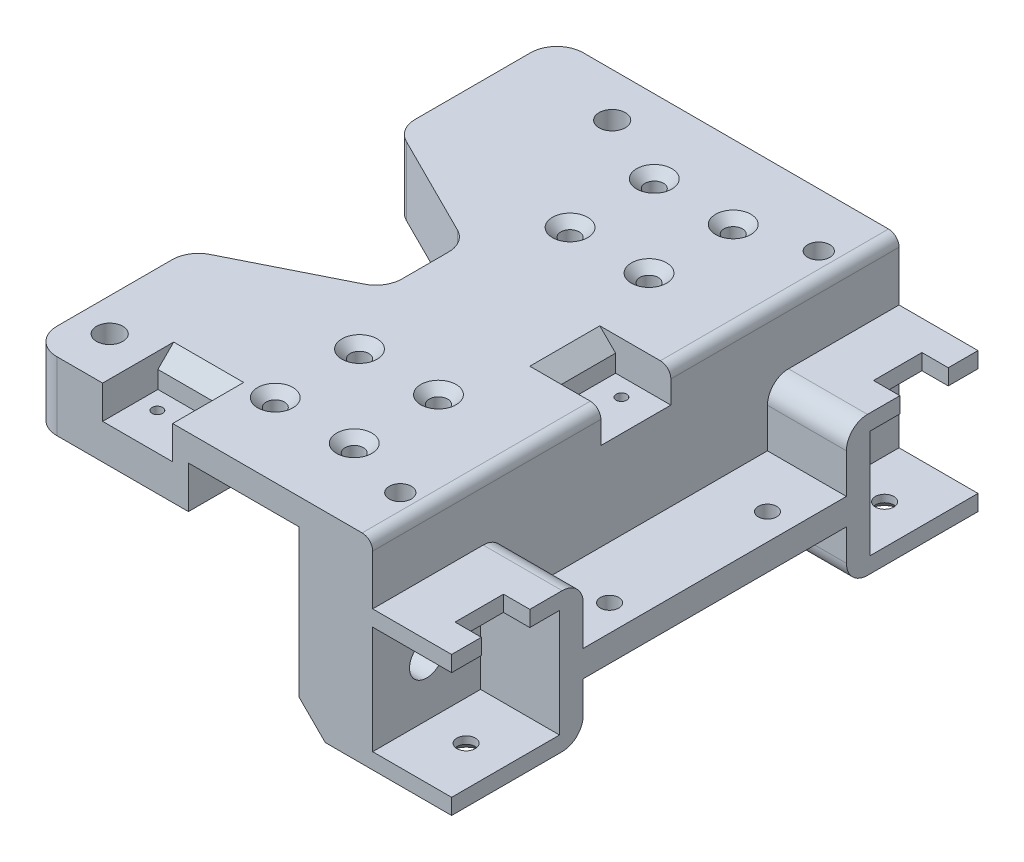
SolidWorks part; units mm, degrees
ref_plane "Front Plane" through (0, 0, 0) normal (0, 0, 1) x (1, 0, 0)
ref_plane "Top Plane" through (0, 0, 0) normal (0, 1, 0) x (1, 0, 0)
ref_plane "Right Plane" through (0, 0, 0) normal (1, 0, 0) x (0, 0, -1)
sketch "Sketch1" plane through (0, 0, 0) normal (0, 1, 0) x (1, 0, 0)
  line L0 (0, 50) -> (0, -50) construction
  line L1 (-10, 50) -> (10, 50)
  line L2 (-10, 50) -> (-10, -50)
  line L3 (-10, -50) -> (10, -50)
  line L4 (10, 50) -> (10, -50) construction
  line L5 (-10, 50) -> (10, -50) construction
  line L6 (-10, -50) -> (10, 50) construction
  line L7 (-7.5, 36) -> (7.5, 36) construction
  line L8 (-7.5, 36) -> (7.5, 20) construction
  line L9 (-10, 0) -> (10, 0) construction
  line L10 (-7.5, -36) -> (7.5, -20) construction
  line L11 (-7.5, -36) -> (7.5, -36) construction
  line L12 (-7.5, 20) -> (7.5, 20) construction
  line L13 (10, 50) -> (11, 50)
  line L14 (11, 50) -> (11, -50)
  line L15 (11, -50) -> (10, -50)
  circle A0 centre (-7.5, 36) radius 1.75
  circle A1 centre (7.5, 36) radius 1.75
  circle A2 centre (-7.5, 20) radius 1.75
  circle A3 centre (7.5, 20) radius 1.75
  circle A4 centre (7.5, -20) radius 1.75
  circle A5 centre (-7.5, -20) radius 1.75
  circle A6 centre (7.5, -36) radius 1.75
  circle A7 centre (-7.5, -36) radius 1.75
  point P0 (0, 0)
  point P16 (0, 36)
  dimension "D2" = 3.5
  dimension "D1" = 20
  dimension "D3" = 15
  dimension "D4" = 16
  dimension "D5" = 100
  dimension "D6" = 20
  dimension "D7" = 1
extrude "Boss-Extrude1" add sketch "Sketch1" along normal blind 5
sketch "Sketch2" plane through (11, 0, 0) normal (1, 0, 0) x (0, 0, -1)
  line L1 (-50, 5) -> (50, 5)
  line L2 (-50, 5) -> (-50, -33)
  line L3 (-50, -33) -> (50, -33)
  line L5 (50, 5) -> (50, -33)
  line L6 (50, 5) -> (50, 0) construction
  line L7 (-50, 5) -> (-50, 0) construction
  line L8 (-50, 5) -> (50, 5) construction
  dimension "D1" = 38
extrude "Boss-Extrude2" add sketch "Sketch2" along normal blind 14
sketch "Sketch3" plane through (25, 0, 0) normal (1, 0, 0) x (0, 0, -1)
  line L0 (0, 5) -> (0, -33) construction
  line L1 (-25, -18) -> (25, -18)
  line L2 (-25, -18) -> (-25, -23)
  line L3 (-25, -23) -> (25, -23)
  line L4 (25, -18) -> (25, -23)
  line L5 (50, 5) -> (-50, 5) construction
  line L6 (-50, -33) -> (50, -33) construction
  point P10 (0, -18)
  dimension "D1" = 5
  dimension "D2" = 50
  dimension "D3" = 10
extrude "Boss-Extrude3" add sketch "Sketch3" along normal blind 15
sketch "Sketch4" plane through (0, -18, 0) normal (0, 1, 0) x (1, 0, 0)
  line L0 (30, 0) -> (40, 0) construction
  line L2 (40, 25) -> (40, -25) construction
  line L3 (35, -15) -> (35, 15) construction
  circle A0 centre (35, 15) radius 1.75
  circle A1 centre (35, -15) radius 1.75
  point P8 (35, 0)
  dimension "D1" = 30
  dimension "D2" = 3.5
  dimension "D3" = 10
extrude "Cut-Extrude1" cut sketch "Sketch4" against normal through all
sketch "Sketch8" plane through (25, 0, 0) normal (1, 0, 0) x (0, 0, -1)
  line L0 (-50, 5) -> (-50, -33) construction
  line L1 (-50, -6.5) -> (-25, -6.5)
  line L2 (-50, -6.5) -> (-50, -9.5)
  line L3 (-50, -33) -> (-25, -33)
  line L4 (-25, -6.5) -> (-25, -33)
  line L5 (-50, -30) -> (-50, -33)
  line L6 (-50, -30) -> (-29.5, -30)
  line L8 (-50, -9.5) -> (-29.5, -9.5)
  line L9 (-29.5, -30) -> (-29.5, -9.5)
  line L10 (0, 20.9) -> (0, -20.9) construction
  line L11 (29.5, -30) -> (29.5, -9.5)
  line L12 (50, -9.5) -> (29.5, -9.5)
  line L13 (50, -30) -> (29.5, -30)
  line L14 (50, -30) -> (50, -33)
  line L15 (25, -6.5) -> (25, -33)
  line L16 (50, -33) -> (25, -33)
  line L17 (50, -6.5) -> (50, -9.5)
  line L18 (50, -6.5) -> (25, -6.5)
  line L19 (-50, -33) -> (50, -33) construction
  line L20 (-25, -18) -> (-25, -23) construction
  dimension "D1" = 3
  dimension "D3" = 3
  dimension "D4" = 20.5
  dimension "D5" = 20.5
extrude "Boss-Extrude6" add sketch "Sketch8" along normal blind 15
sketch "Sketch9" plane through (25, 0, 0) normal (1, 0, 0) x (0, 0, -1)
  line L0 (-50, -9.5) -> (-29.5, -30) construction
  line L1 (50, -9.5) -> (29.5, -30) construction
  circle A0 centre (-39.75, -19.75) radius 3.25
  circle A1 centre (39.75, -19.75) radius 3.25
  dimension "D1" = 6.5
extrude "Cut-Extrude3" cut sketch "Sketch9" against normal through all
sketch "Sketch10" plane through (11, 0, 0) normal (-1, 0, 0) x (0, 0, 1)
  circle A0 centre (-39.75, -19.75) radius 5.25
  circle A1 centre (39.75, -19.75) radius 5.25
  dimension "D1" = 10.5
extrude "Cut-Extrude4" cut sketch "Sketch10" against normal offset from surface (9 mm away) 5 up to face at (25, -19.75, 36.5)
sketch "Sketch11" plane through (0, -6.5, 0) normal (0, 1, 0) x (1, 0, 0)
  line L0 (40, -25) -> (40, -50) construction
  line L1 (40, -35.15) -> (35, -35.15)
  line L2 (40, -35.15) -> (40, -44.35)
  line L3 (40, -44.35) -> (35, -44.35)
  line L4 (35, -35.15) -> (35, -44.35)
  line L5 (35, -39.75) -> (40, -39.75) construction
  line L7 (-10, 0) -> (40, 0) construction
  line L8 (-10, 50) -> (-10, -50) construction
  line L9 (40, 25) -> (40, -25) construction
  line L10 (40, -35.15) -> (35, -35.15)
  line L11 (40, -44.35) -> (35, -44.35)
  line L12 (35, 39.75) -> (40, 39.75) construction
  line L13 (40, 44.35) -> (35, 44.35)
  line L14 (40, 35.15) -> (35, 35.15)
  line L15 (35, 35.15) -> (35, 44.35)
  line L16 (40, 44.35) -> (35, 44.35)
  line L17 (40, 35.15) -> (40, 44.35)
  line L18 (40, 35.15) -> (35, 35.15)
  line L19 (40, -50) -> (40, -29.5) construction
  point P22 (40, -39.75)
  line M7 (40, -50) -> (40, -25)
  dimension "D1" = 9.2
  dimension "D3" = 5
extrude "Cut-Extrude5" cut sketch "Sketch11" against normal up to next contours L1 L4 L3 M7 | L14 L17 L13 L15 region at (37.5, -6.5, 39.75) region at (37.5, -6.5, -39.75)
sketch "Sketch12" plane through (0, -30, 0) normal (0, 1, 0) x (1, 0, 0)
  line L0 (40, -39.75) -> (25, -39.75) construction
  line L1 (40, -29.5) -> (40, -50) construction
  line L2 (25, -25) -> (25, -50) construction
  line L3 (-20.9, 0) -> (20.9, 0) construction
  circle A0 centre (32.5, -39.75) radius 1.75
  circle A2 centre (32.5, 39.75) radius 1.75
  dimension "D1" = 3.5
extrude "Cut-Extrude6" cut sketch "Sketch12" against normal through all
sketch "Sketch13" plane through (-10, 0, 0) normal (-1, 0, 0) x (0, 0, 1)
  line L1 (-50, 5) -> (50, 5)
  line L2 (-50, 5) -> (-50, -8)
  line L3 (-50, -8) -> (50, -8)
  line L4 (50, 5) -> (50, -8)
  dimension "D1" = 13
extrude "Boss-Extrude7" add sketch "Sketch13" along normal blind 30
sketch "Sketch14" plane through (0, 5, 0) normal (0, 1, 0) x (1, 0, 0)
  line L6 (-27.65, 41.65) -> (-27.65, -41.23) construction
  line L12 (-21.15, 35.15) -> (40, 35.15) construction
  line L18 (-33.73, -35.15) -> (40, -35.15) construction
  circle A0 centre (-21.15, 41.65) radius 2.5
  circle A1 centre (-33.73, -41.23) radius 2.5
  circle A2 centre (-33.73, -41.23) radius 6.08 construction
  circle A3 centre (-21.15, 41.65) radius 6.5 construction
  dimension "D1" = 5
  dimension "D2" = 5
  dimension "D4" = 12.16
  dimension "D5" = 13
  dimension "D3" = 21.15
extrude "Cut-Extrude7" cut sketch "Sketch14" against normal through all
sketch "Sketch15" plane through (0, -8, 0) normal (0, -1, 0) x (1, 0, 0)
  line L0 (-40, -50) -> (-40, 50) construction
  line L1 (-29.63, 43.5971) -> (-33.73, 45.9643)
  line L2 (-33.73, 45.9643) -> (-37.83, 43.5971)
  line L3 (-37.83, 43.5971) -> (-37.83, 38.8629)
  line L4 (-37.83, 38.8629) -> (-33.73, 36.4957)
  line L5 (-33.73, 36.4957) -> (-29.63, 38.8629)
  line L6 (-29.63, 38.8629) -> (-29.63, 43.5971)
  line L7 (-17.05, -44.0171) -> (-17.05, -39.2829)
  line L8 (-17.05, -39.2829) -> (-21.15, -36.9157)
  line L9 (-21.15, -36.9157) -> (-25.25, -39.2829)
  line L10 (-25.25, -39.2829) -> (-25.25, -44.0171)
  line L11 (-25.25, -44.0171) -> (-21.15, -46.3843)
  line L12 (-21.15, -46.3843) -> (-17.05, -44.0171)
  circle A0 centre (-33.73, 41.23) radius 4.1 construction
  circle A1 centre (-21.15, -41.65) radius 4.1 construction
  dimension "D1" = 8.2
extrude "Cut-Extrude8" cut sketch "Sketch15" against normal blind 5
sketch "Sketch16" plane through (0, 5, 0) normal (0, 1, 0) x (1, 0, 0)
  line L0 (20, 39.75) -> (40, 39.75) construction
  line L1 (40, 39.75) -> (40, -39.75) construction
  line L2 (40, -39.75) -> (20, -39.75) construction
  line L3 (20, -39.75) -> (20, 39.75) construction
  line L4 (40, 50) -> (40, 29.5) construction
  line L5 (40, -29.5) -> (40, -50) construction
  circle A0 centre (20, 39.75) radius 2.1
  circle A1 centre (20, -39.75) radius 2.1
  dimension "D1" = 4.2
  dimension "D2" = 4.2
  dimension "D3" = 20
extrude "Cut-Extrude9" cut sketch "Sketch16" against normal blind 4
chamfer "Chamfer1" distance 1.6 angle 45 8 edges at (7.5, 5, 34.25) (-7.5, 5, 34.25) (7.5, 5, 18.25) (-7.5, 5, 18.25) (7.5, 5, -18.25) (-7.5, 5, -18.25) (7.5, 5, -34.25) (-7.5, 5, -34.25)
sketch "Sketch17" plane through (0, 5, 0) normal (0, 1, 0) x (1, 0, 0)
  line L0 (-40, 20) -> (-15, 7.5)
  line L1 (-40, -50) -> (-40, 50) construction
  line L2 (-15, 7.5) -> (-15, -7.5)
  line L3 (-15, -7.5) -> (-40, -20)
  line L4 (-40, -20) -> (-40, 20)
  point P5 (-15, 0)
  dimension "D1" = 15
  dimension "D2" = 25
  dimension "D3" = 40
extrude "Cut-Extrude10" cut sketch "Sketch17" against normal through all
chamfer "Chamfer2" distance 1.6 angle 45 2 edges at (32.5, -33, -41.5) (32.5, -33, 41.5)
chamfer "Chamfer3" distance 5 angle 45 1 edges at (11, -33, 0)
sketch "Sketch18" plane through (0, 1, 0) normal (0, 1, 0) x (1, 0, 0)
  circle A0 centre (20, 39.75) radius 1.75
  circle A1 centre (20, -39.75) radius 1.75
  dimension "D1" = 3.5
  dimension "D2" = 3.5
extrude "Cut-Extrude11" cut sketch "Sketch18" against normal blind 4
fillet "Fillet1" radius 5 6 edges at (-40, -1.5, 50) (-40, -1.5, 20) (-15, -1.5, 7.5) (-15, -1.5, -7.5) (-40, -1.5, -20) (-40, -1.5, -50)
fillet "Fillet2" radius 4 4 edges at (32.5, -33, -25) (32.5, -6.5, -25) (32.5, -33, 25) (32.5, -6.5, 25)
sketch "Sketch19" plane through (25, 0, 0) normal (1, 0, 0) x (0, 0, -1)
  line L0 (50, 5) -> (-50, 5) construction
  line L1 (-6.65, 5) -> (6.65, 5)
  line L2 (-6.65, 5) -> (-6.65, -1.3)
  line L3 (-6.65, -1.3) -> (6.65, -1.3)
  line L4 (6.65, 5) -> (6.65, -1.3)
  point P7 (0, 5)
  dimension "D1" = 13.3
  dimension "D2" = 6.3
extrude "Cut-Extrude12" cut sketch "Sketch19" against normal blind 10.5
sketch "Sketch20" plane through (0, -1.3, 0) normal (0, 1, 0) x (1, 0, 0)
  line L0 (19, 3.25) -> (19, -3.25) construction
  line L3 (14.5, 6.65) -> (14.5, -6.65) construction
  line L4 (18, 3.25) -> (18, -3.25) construction
  circle A0 centre (19, 3.25) radius 1
  circle A1 centre (19, -3.25) radius 1
  point P2 (14.5, 0)
  point P3 (19, 0)
  dimension "D1" = 2
  dimension "D2" = 6.5
  dimension "D3" = 3.5
extrude "Cut-Extrude13" cut sketch "Sketch20" against normal blind 3
chamfer "Chamfer4" distance 3 angle 45 1 edges at (14.5, 5, 0)
fillet "Fillet3" radius 2 2 edges at (25, 5, -28.325) (25, 5, 28.325)
sketch "Sketch22" plane through (0, 5, 0) normal (0, 1, 0) x (1, 0, 0)
  line L0 (-35, -50) -> (23, -50) construction
  line L1 (-26.3, -50) -> (-13, -50)
  line L2 (-26.3, -50) -> (-26.3, -39.5)
  line L3 (-26.3, -39.5) -> (-13, -39.5)
  line L4 (-13, -50) -> (-13, -39.5)
  line L5 (-10, 50) -> (-10, -50) construction
  dimension "D1" = 10.5
  dimension "D2" = 13.3
  dimension "D3" = 3
extrude "Cut-Extrude14" cut sketch "Sketch22" against normal blind 6.3
sketch "Sketch23" plane through (0, -1.3, 0) normal (0, 1, 0) x (1, 0, 0)
  line L0 (-22.9, -43) -> (-16.4, -43) construction
  line L1 (-13, -39.5) -> (-26.3, -39.5) construction
  line L2 (-26.3, -50) -> (-13, -50) construction
  circle A0 centre (-22.9, -43) radius 1
  circle A1 centre (-16.4, -43) radius 1
  point P9 (-19.65, -50)
  point P10 (-19.65, -43)
  dimension "D1" = 2
  dimension "D2" = 2
  dimension "D3" = 6.5
  dimension "D4" = 3.5
extrude "Cut-Extrude15" cut sketch "Sketch23" against normal blind 3
chamfer "Chamfer5" distance 3 angle 45 1 edges at (-19.65, 5, 39.5)
